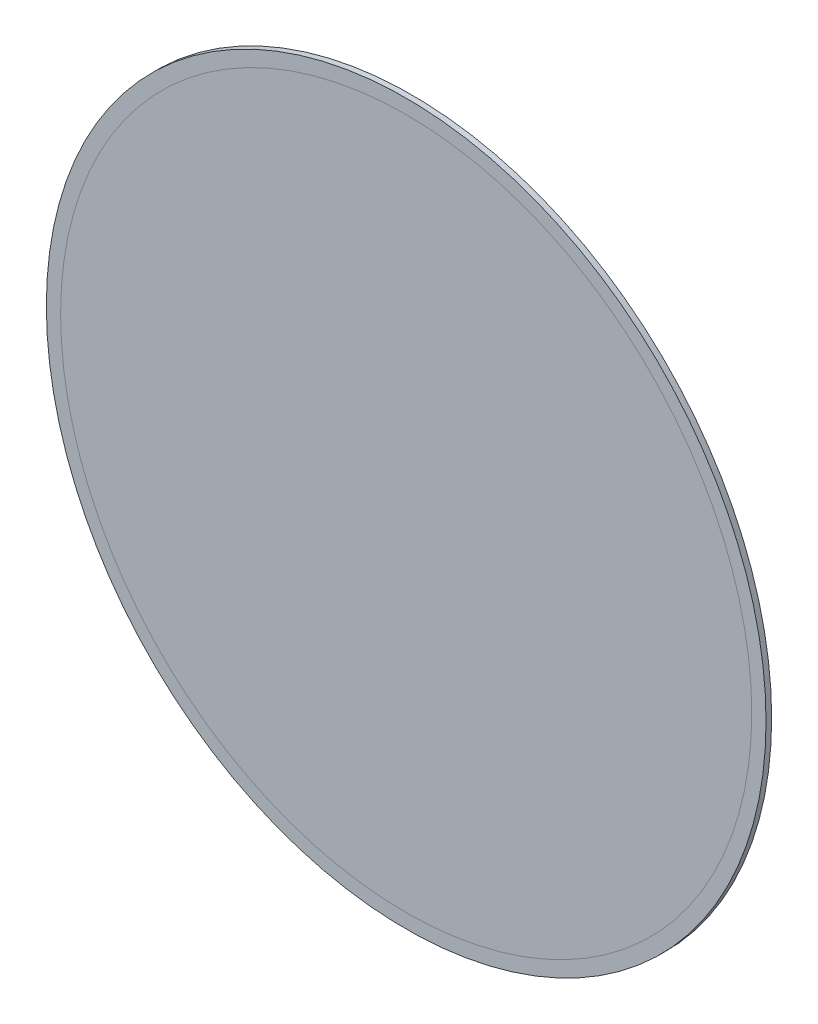
SolidWorks part; units mm, degrees
ref_plane "Front" through (0, 0, 0) normal (0, 0, 1) x (1, 0, 0)
ref_plane "Top" through (0, 0, 0) normal (0, 1, 0) x (1, 0, 0)
ref_plane "Right" through (0, 0, 0) normal (1, 0, 0) x (0, 0, -1)
sketch "Sketch1" plane through (0, 0, 0) normal (0, 0, 1) x (1, 0, 0)
  circle A0 centre (0, 0) radius 320
extrude "Quartz Window Thickness = 5 mm" add sketch "Sketch1" along normal blind 5
ref_plane "Ref Plane to Project Split Line" through (0, 0, 15) normal (0, 0, 1) x (1, 0, 0)
sketch "Sketch2" plane through (0, 0, 15) normal (0, 0, 1) x (1, 0, 0)
  circle A0 centre (0, 0) radius 307.3
split line "Split Line2"
ref_axis "Axis1" through (0, 0, -80.9) along (0, 0, 1)
